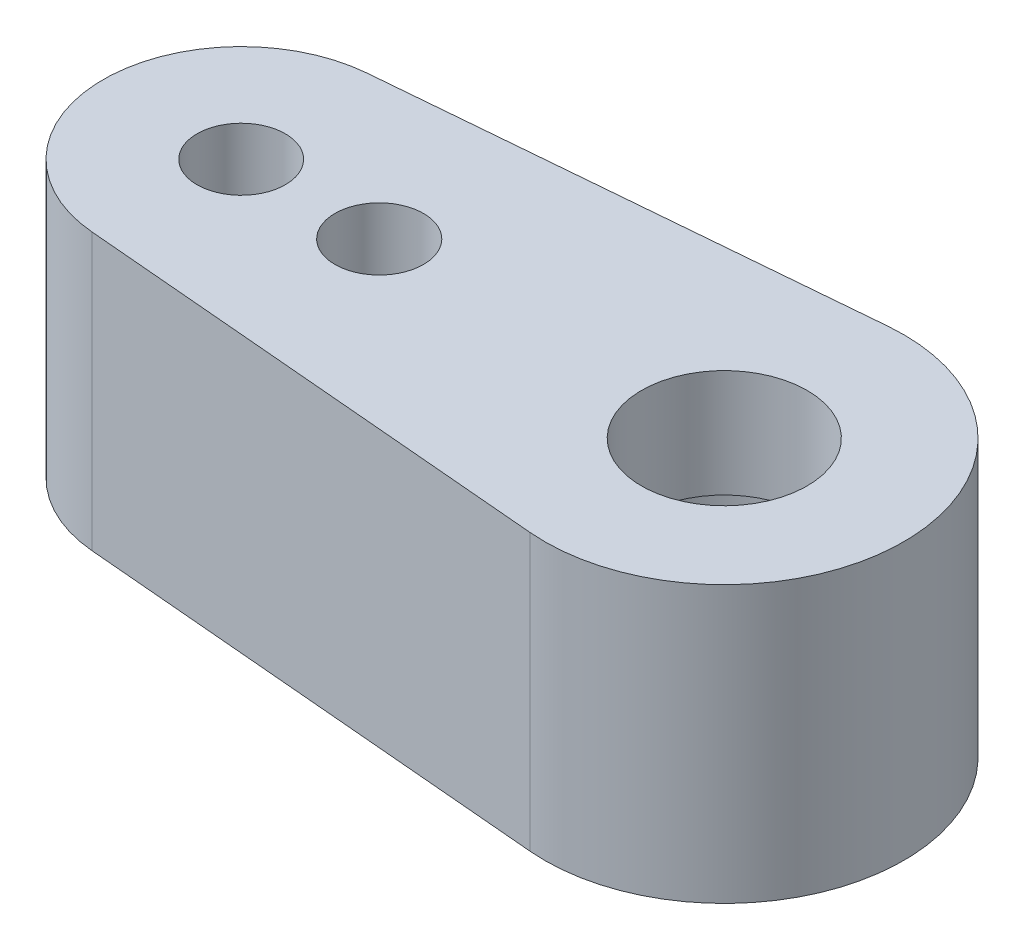
SolidWorks part; units mm, degrees
ref_plane "Front Plane" through (0, 0, 0) normal (0, 0, 1) x (1, 0, 0)
ref_plane "Top Plane" through (0, 0, 0) normal (0, 1, 0) x (1, 0, 0)
ref_plane "Right Plane" through (0, 0, 0) normal (1, 0, 0) x (0, 0, -1)
sketch "Sketch1" plane through (0, 0, 0) normal (0, 1, 0) x (1, 0, 0)
  line L0 (-3.5857, 0.9963) -> (-0.1114, 1.2952)
  line L1 (-3.5857, -0.9963) -> (-0.1114, -1.2952)
  line L2 (-2.5, 0) -> (0, 0) construction
  line L3 (-2.5, 0) -> (-3.5, 0) construction
  arc A0 (-0.1114, -1.2952) -> (-0.1114, 1.2952) centre (0, 0) ccw
  arc A1 (-3.5857, -0.9963) -> (-3.5857, 0.9963) centre (-3.5, 0) cw
  point P1 (-3.5, 0)
  dimension "D1" = 1
  dimension "D2" = 2.6
  dimension "D4" = 1
  dimension "D3" = 2.5
extrude "Boss-Extrude1" add sketch "Sketch1" along normal blind 1 and the other way blind 1
sketch "Sketch4" plane through (0, 0, 0) normal (0, 0, 1) x (1, 0, 0)
  line L0 (0.85, 0) -> (0.85, 0.075)
  line L1 (0.85, 0.075) -> (0.6, 0.2193)
  line L2 (0.6, 0.2193) -> (0.6, 1)
  line L3 (1.3, 1) -> (-0.1114, 1) construction
  line L4 (0, 0) -> (0.85, 0) construction
  line L5 (0.85, 0) -> (0.85, -0.075)
  line L6 (0.85, -0.075) -> (0.6, -0.2193)
  line L7 (-0.1114, -1) -> (1.3, -1) construction
  line L9 (0, -1) -> (0, 1)
  line L10 (0, 1) -> (0.6, 1)
  line L11 (0.6, -0.2193) -> (0.6, -1)
  line L12 (0, -1) -> (0.6, -1)
  dimension "D1" = 0.075
  dimension "D2" = 120
  dimension "D3" = 0.25
  dimension "D4" = 0.6
revolve "Cut-Revolve1" cut sketch "Sketch4" angle 360 about L9
sketch "Sketch5" plane through (0, 1, 0) normal (0, 1, 0) x (1, 0, 0)
  circle A0 centre (-2.5, 0) radius 0.3207
  circle A1 centre (-3.5, 0) radius 0.32
  dimension "D1" = 0.6414
  dimension "D2" = 0.64
extrude "Cut-Extrude1" cut sketch "Sketch5" against normal up to next
